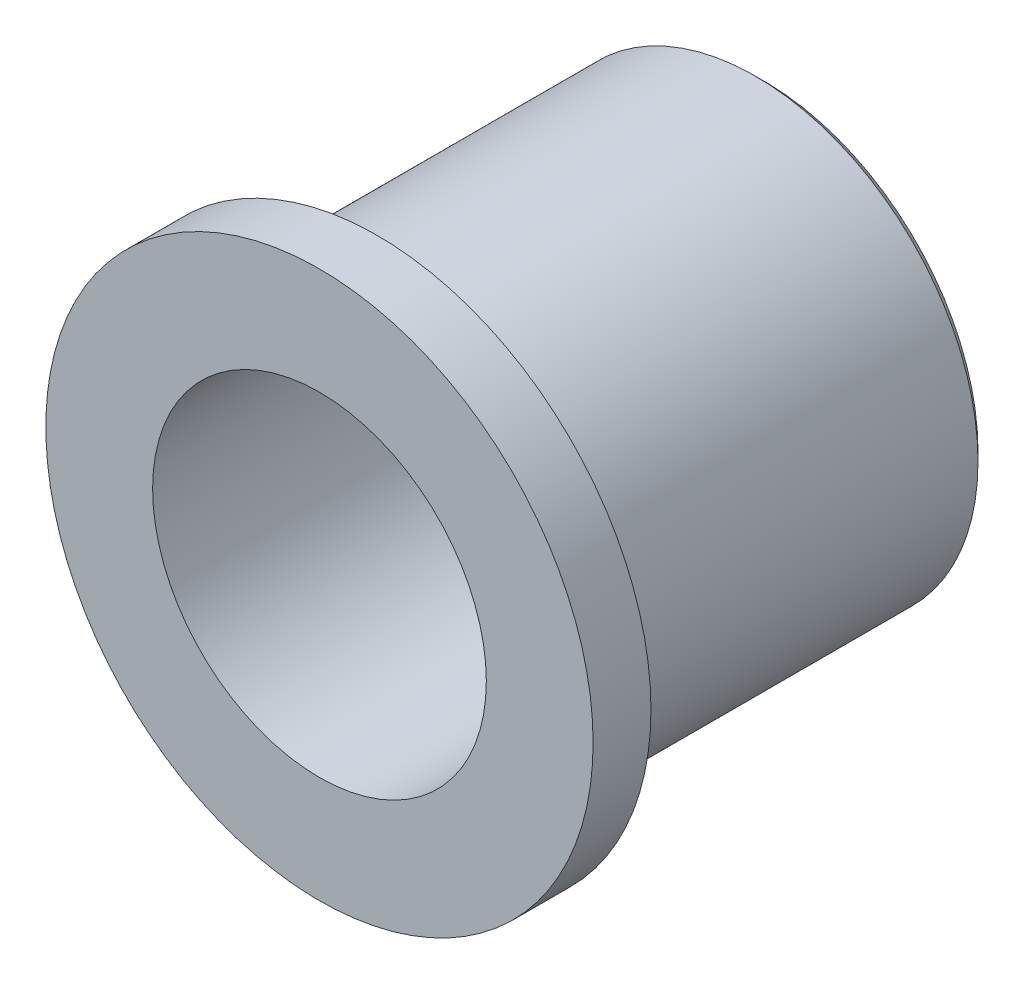
SolidWorks part; units mm, degrees
material "ABS PC"
ref_plane "Front Plane" through (0, 0, 0) normal (0, 0, 1) x (1, 0, 0)
ref_plane "Top Plane" through (0, 0, 0) normal (0, 1, 0) x (1, 0, 0)
ref_plane "Right Plane" through (0, 0, 0) normal (1, 0, 0) x (0, 0, -1)
ref_axis "X-axis" through (-88.99, 0, 0) along (1, 0, 0)
ref_axis "Y-axis" through (0, 55, 0) along (0, -1, 0)
ref_axis "Z-axis" through (0, 0, -88.99) along (0, 0, 1)
sketch "Sketch1" plane through (0, 0, 0) normal (1, 0, 0) x (0, 0, -1)
  line L0 (0, 0) -> (21.3102, 0) construction
  line L1 (0, 0) -> (-25.4, 0)
  line L2 (-25.4, 0) -> (-25.4, 15.621)
  line L3 (-25.4, 15.621) -> (-22.098, 15.621)
  line L4 (-22.098, 15.621) -> (-22.098, 12.7)
  line L5 (-22.098, 12.7) -> (0, 12.7)
  line L6 (0, 12.7) -> (0, 0)
  dimension "D1" = 25.4
  dimension "D2" = 3.302
  dimension "D3" = 31.242
  dimension "D4" = 25.4
revolve "Revolve1" add sketch "Sketch1" angle 360 about L0
hole_wizard "1/4 (0.75) Diameter Hole1" positions "Sketch2" profile "Sketch3" hole size "1/4" standard "ANSI Inch" end condition through all
sketch "Sketch2" plane through (0, 0, 25.4) normal (0, 0, 1) x (1, 0, 0)
  point P0 (0, 0)
sketch "Sketch3" plane through (0, 0, 25.4) normal (1, 0, 0) x (0, -1, 0)
  line L0 (0, 0) -> (0, 25.4)
  line L1 (0, 25.4) -> (9.525, 25.4)
  line L2 (9.525, 25.4) -> (9.525, 0)
  line L5 (9.525, 0) -> (0, 0)
  line L11 (0, -6.35) -> (0, 107.95) construction
  dimension "Thru Hole Dia." = 19.05
  dimension "Thru Hole Depth" = 25.4
chamfer "Chamfer1" distance 0.508 angle 45 1 edges at (12.7, 0, 0)
